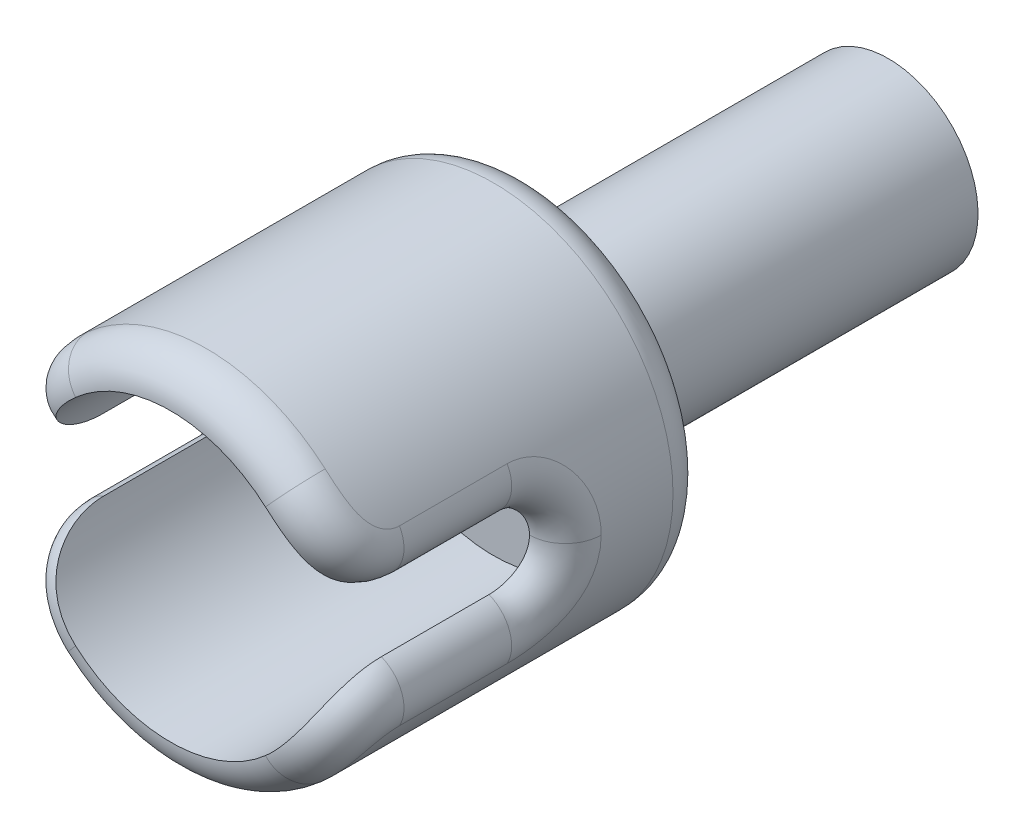
SolidWorks part; units mm, degrees
note: The reader was unsure of these and kept them because the rebuilt part matched: shared geometry of "Sketch1<4>".
material "AISI 1045 Steel, cold drawn"
ref_plane "Front Plane" through (0, 0, 0) normal (1, 0, 0) x (0, 1, 0)
ref_plane "Top Plane" through (0, 0, 0) normal (0, 0, 1) x (0, 1, 0)
ref_plane "Right Plane" through (0, 0, 0) normal (0, 1, 0) x (-1, 0, 0)
sketch "Sketch1" plane through (0, 0, 0) normal (1, 0, 0) x (0, 1, 0)
  line L0 (-8.6093, 0) -> (10.7548, 0) construction
  line L1 (0, 8.7222) -> (0, -9.4734) construction
  line L2 (3, 10) -> (0, 10)
  line L3 (3, 10) -> (5, 10)
  line L4 (5, 10) -> (5, 0)
  line L5 (5, 0) -> (2.5, 0)
  line L6 (2.5, 0) -> (2.5, -10)
  line L7 (2.5, -10) -> (0, -10)
  line L8 (0, -10) -> (0, 0)
  line L9 (0, 0) -> (2.5, 0)
  line L10 (5, 2) -> (0, 2)
  line L11 (0, 2) -> (0, 0)
  line L12 (0, 4) -> (0, 0)
  line L13 (0, 10) -> (0, 4)
  dimension "D1" = 10
  dimension "D2" = 10
  dimension "D3" = 5
  dimension "D6" = 10
  dimension "D7" = 2
  dimension "D8" = 6
revolve "Revolve2" add sketch "Sketch1" angle 360 about L1
shell "Shell1" thickness 1
revolve "Revolve3" add sketch "Sketch1<4>" angle 360 about L12
sketch "Sketch1<4>" plane through (0, 0, 0) normal (1, 0, 0) x (0, 1, 0) same geometry as "Sketch1"
sketch "Sketch2" plane through (0, 0, 0) normal (1, 0, 0) x (0, 1, 0)
  line L2 (-1, 8) -> (-1, 4)
  line L3 (-1, 4) -> (1, 4)
  line L4 (1, 8) -> (1, 4)
  line L5 (5, 10) -> (-5, 10) construction
  line L6 (0, 10.9867) -> (0, 1.7027) construction
  line L7 (5, 10) -> (-5, 10)
  circle A0 centre (-3, 8) radius 2
  circle A1 centre (3, 8) radius 2
  point P4 (0, 4)
  dimension "D3" = 4
  dimension "D1" = 2
  dimension "D2" = 6
extrude "Cut-Extrude2" cut sketch "Sketch2" against normal through all both and the other way through all contours L7 L6 L3 L4 A1 | L6 L7 A0 L2 L3
fillet "Fillet2" radius 1 4 edges at (4, 0, 4) (5, 0, 4) (4.386, 1, 4) (4.386, -1, 4)
fillet "Fillet3" radius 1 4 edges at (-4, 0, 4) (-5, 0, 4) (-4.386, 1, 4) (-4.386, -1, 4)
fillet "Fillet4" radius 1 9 edges at (5, 0, 4) (-4.6909, 1.7306, 9.5455) (4.7958, 1.4142, 9.2187) (0, 5, 10) (-5, 0, 4) (4.7958, -1.4142, 9.2187) (-4.6909, -1.7306, 9.5455) (0, -5, 10) (5, 0, 0)
ref_point "Point1"
ref_plane "Plane1" through (0, 0, 10) normal (0, 0, -1) x (0, 1, 0)
ref_point "Point2"
